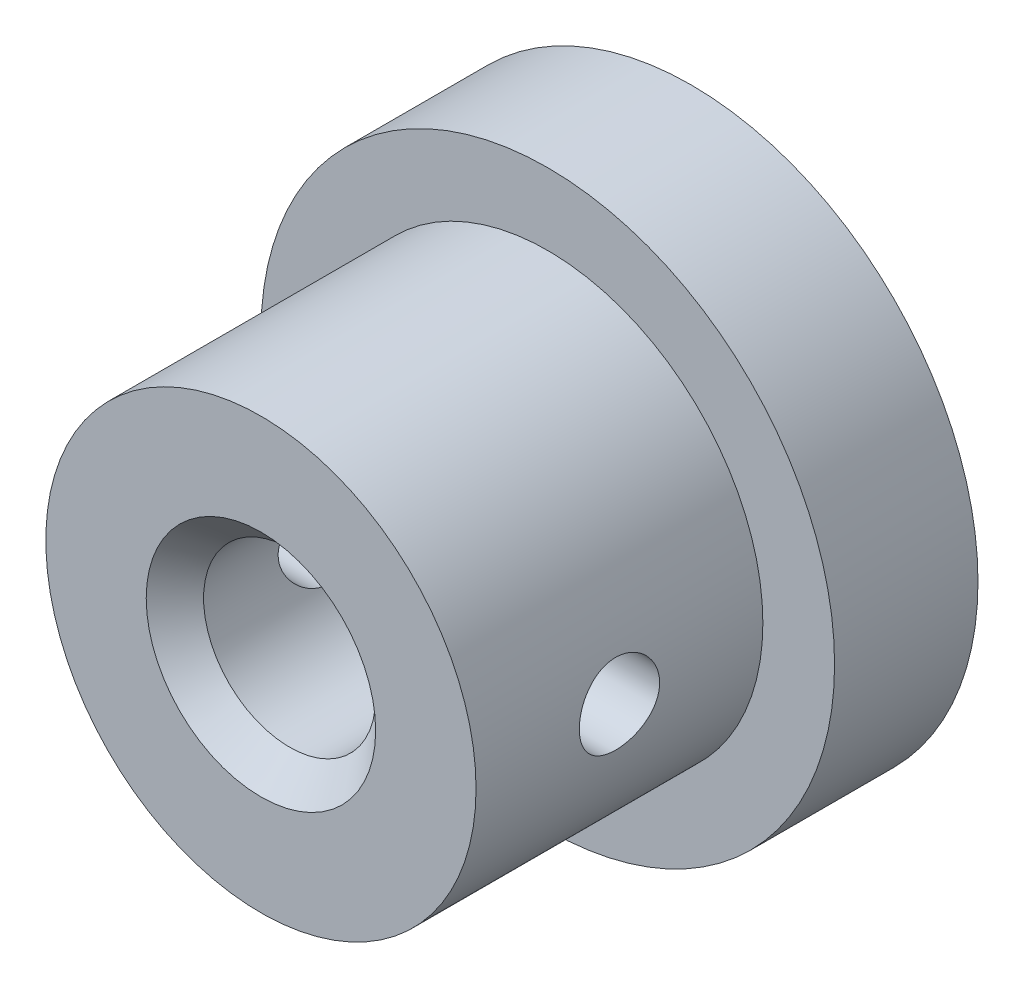
SolidWorks part; units mm, degrees
ref_plane "정면" through (0, 0, 0) normal (0, 0, 1) x (1, 0, 0)
ref_plane "윗면" through (0, 0, 0) normal (0, 1, 0) x (1, 0, 0)
ref_plane "우측면" through (0, 0, 0) normal (1, 0, 0) x (0, 0, -1)
sketch "스케치1" plane through (0, 0, 0) normal (0, 0, 1) x (1, 0, 0)
  circle A0 centre (0, 0) radius 10
  circle A1 centre (0, 0) radius 7.5
  circle A2 centre (0, 0) radius 3
  dimension "D1" = 20
  dimension "D2" = 6
  dimension "D3" = 15
extrude "보스-돌출1" add sketch "스케치1" along normal blind 15 contours A1 A2 region at (-7.2879, 0, 0)
extrude "보스-돌출2" add sketch "스케치1<3>" along normal blind 5 contours A0 A1 region at (-9.7172, 0, 0)
sketch "스케치1<3>" plane through (0, 0, 0) normal (0, 0, 1) x (1, 0, 0) same geometry as "스케치1"
sketch "스케치2" plane through (0, 0, 0) normal (1, 0, 0) x (0, 0, -1)
  line L0 (0, 0) -> (-15, 0) construction
  circle A0 centre (-10, 0) radius 1.4
  dimension "D2" = 2.8
  dimension "D1" = 15
  dimension "D3" = 5
extrude "컷-돌출1" cut sketch "스케치2" against normal mid plane 45
chamfer "모따기1" distance 1 angle 45 2 edges at (3, 0, 15) (3, 0, 0)
